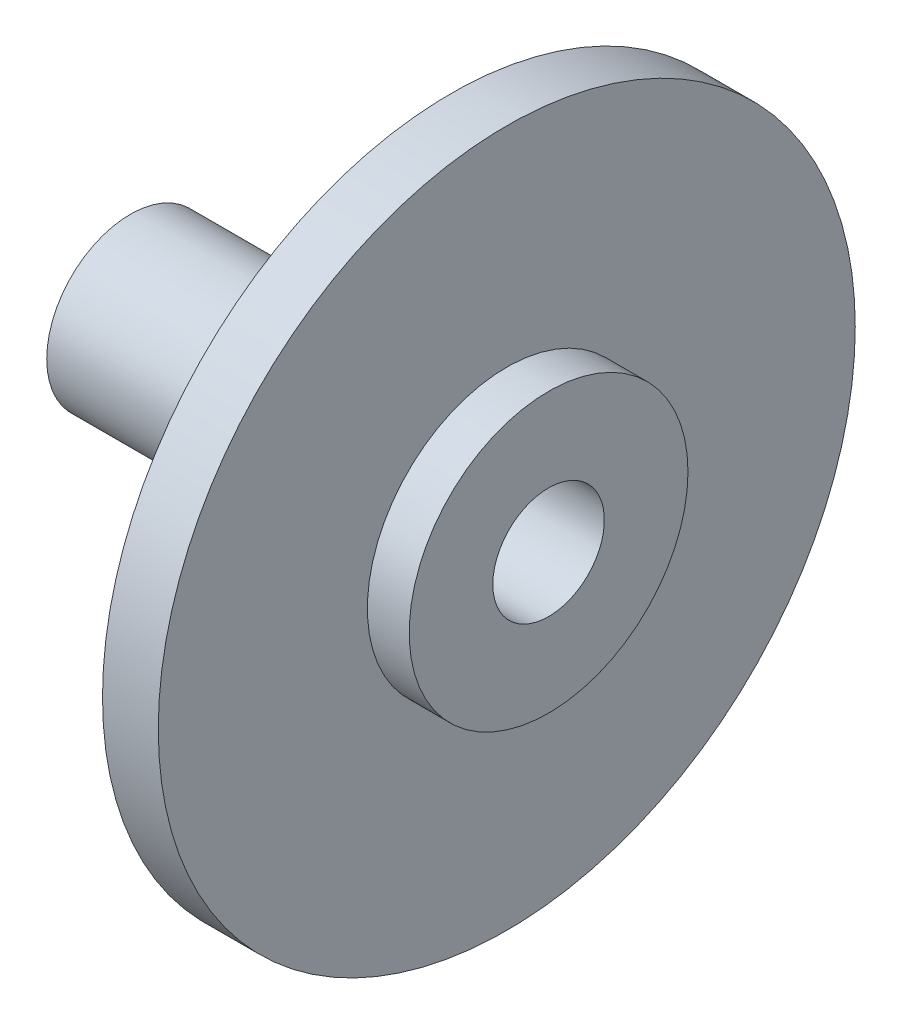
SolidWorks part; units mm, degrees
ref_plane "Front Plane" through (0, 0, 0) normal (0, 0, 1) x (1, 0, 0)
ref_plane "Top Plane" through (0, 0, 0) normal (0, 1, 0) x (1, 0, 0)
ref_plane "Right Plane" through (0, 0, 0) normal (1, 0, 0) x (0, 0, -1)
sketch "Sketch1" plane through (0, 0, 0) normal (1, 0, 0) x (0, 0, -1)
  circle A0 centre (0, 0) radius 25
extrude "Boss-Extrude1" add sketch "Sketch1" along normal mid plane 4
sketch "Sketch2" plane through (-2, 0, 0) normal (-1, 0, 0) x (0, 0, 1)
  circle A0 centre (0, 0) radius 6
extrude "Boss-Extrude2" add sketch "Sketch2" along normal blind 23
sketch "Sketch3" plane through (2, 0, 0) normal (1, 0, 0) x (0, 0, -1)
  circle A0 centre (0, 0) radius 10
extrude "Boss-Extrude3" add sketch "Sketch3" along normal blind 3
sketch "Sketch4" plane through (-25, 0, 0) normal (-1, 0, 0) x (0, 0, 1)
  circle A0 centre (0, 0) radius 4
extrude "Cut-Extrude1" cut sketch "Sketch4" against normal blind 30
